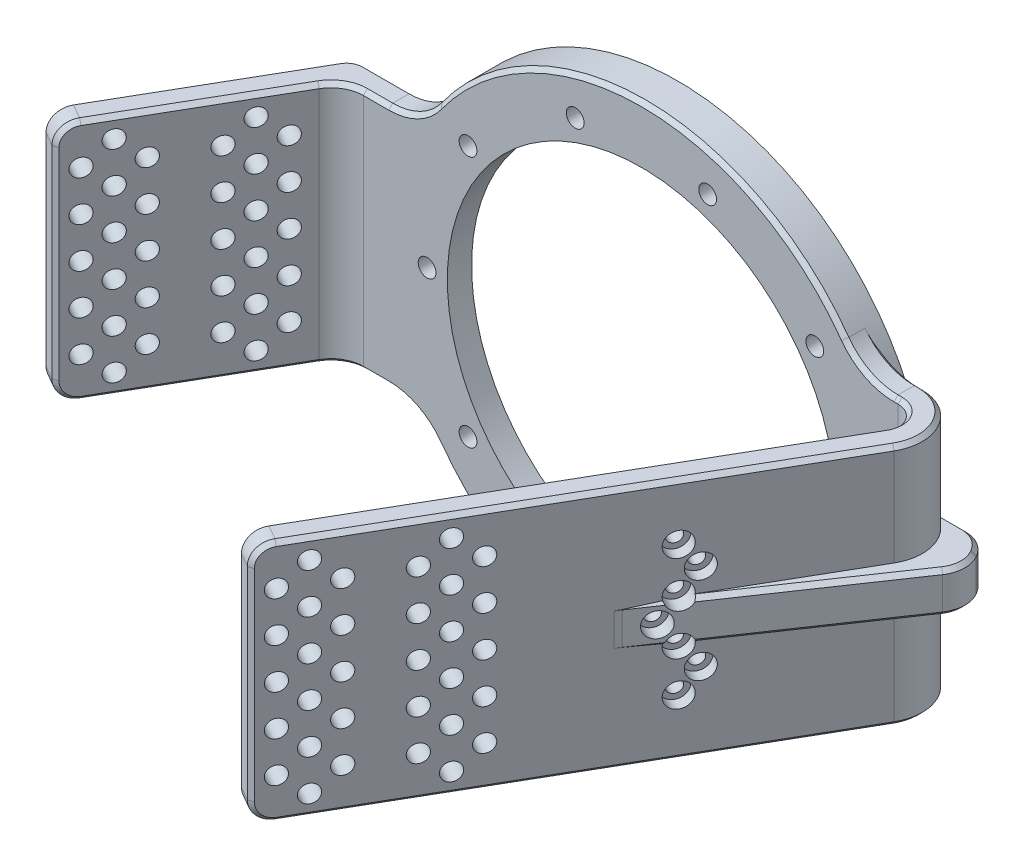
SolidWorks part; units mm, degrees
material "6061 合金"
ref_plane "前视基准面" through (0, 0, 0) normal (0, 0, 1) x (1, 0, 0)
ref_plane "上视基准面" through (0, 0, 0) normal (0, 1, 0) x (1, 0, 0)
ref_plane "右视基准面" through (0, 0, 0) normal (1, 0, 0) x (0, 0, -1)
sketch "草图1" plane through (0, 0, 0) normal (0, 0, 1) x (1, 0, 0)
  line L1 (62, 30) -> (62, -30)
  line L2 (-62, 30) -> (-62, -30)
  line L3 (62, 30) -> (54.2586, 30)
  line L4 (62, -30) -> (54.2586, -30)
  line L5 (-54.2586, 30) -> (-62, 30)
  line L7 (-54.2586, -30) -> (-62, -30)
  arc A0 (43.6921, 30) -> (43.6921, -30) centre (0, 0) ccw construction
  arc A1 (51.9615, 30) -> (-51.9615, 30) centre (0, 0) ccw construction
  circle A2 centre (0, 0) radius 48
  arc A3 (54.2586, 30) -> (-54.2586, 30) centre (0, 0) ccw
  circle A4 centre (0, 0) radius 53 construction
  circle A5 centre (0, 0) radius 60 construction
  circle A6 centre (0, 0) radius 62 construction
  arc A8 (-54.2586, -30) -> (54.2586, -30) centre (0, 0) ccw
  point P12 (62, 0)
  point P15 (-62, 0)
  dimension "D1" = 5
  dimension "D2" = 2
extrude "凸台-拉伸1" add sketch "草图1" along normal blind 6
sketch "草图2" plane through (0, -30, 0) normal (0, -1, 0) x (1, 0, 0)
  line L0 (-99.738, 51.6754) -> (-73.3673, 6)
  line L1 (-104.9342, 48.6754) -> (-76.8314, 0)
  line L2 (-62, 0) -> (-54.2586, 0) construction
  line L3 (-62, 6) -> (-54.2586, 6) construction
  line L4 (-76.8314, 0) -> (-62, 0)
  line L5 (-73.3673, 6) -> (-62, 6)
  line L6 (9.3812, 114.6754) -> (72.125, 6)
  line L7 (14.5773, 117.6754) -> (82.5173, 0)
  line L8 (-104.9342, 48.6754) -> (-81.0842, 7.366) construction
  line L9 (-99.738, 51.6754) -> (-75.888, 10.366) construction
  line L10 (9.3812, 114.6754) -> (33.2312, 73.366) construction
  line L11 (14.5773, 117.6754) -> (38.4273, 76.366) construction
  line L12 (-104.9342, 48.6754) -> (-99.738, 51.6754)
  line L13 (9.3812, 114.6754) -> (14.5773, 117.6754)
  line L14 (-62, 0) -> (-62, 6)
  line L15 (62, 6) -> (62, 0)
  line L16 (62, 6) -> (72.125, 6)
  line L17 (62, 0) -> (82.5173, 0)
  dimension "D1" = 6
  dimension "D2" = 6
extrude "凸台-拉伸2" add sketch "草图2" against normal up to surface (60 mm away) up to face at (-58.1293, 30, 3)
fillet "圆角3" radius 8 1 edges at (-73.3673, 0, 6)
fillet "圆角4" radius 5 1 edges at (-76.8314, 0, 0)
fillet "圆角6" radius 5 4 edges at (11.9793, -30, 116.1754) (11.9793, 30, 116.1754) (-102.3361, 30, 50.1754) (-102.3361, -30, 50.1754)
fillet "圆角7" radius 5 1 edges at (72.125, 0, 6)
fillet "圆角8" radius 11 1 edges at (82.5173, 0, 0)
fillet "圆角9" radius 15 4 edges at (-54.2586, -30, 3) (-54.2586, 30, 3) (54.2586, 30, 3) (54.2586, -30, 3)
sketch "草图3" plane through (61.888, 0, 35.731) normal (0.866, 0, 0.5) x (0.5, 0, -0.866)
  line L1 (-51.9212, 20) -> (-51.9212, -20) construction
  circle A0 centre (-89.6212, 0) radius 2.2
  circle A1 centre (-89.6212, 10) radius 2.2
  circle A2 centre (-89.6212, 20) radius 2.2
  circle A3 centre (-89.6212, -10) radius 2.2
  circle A4 centre (-89.6212, -20) radius 2.2
  circle A5 centre (-83.6212, 5) radius 2.2
  circle A6 centre (-83.6212, 15) radius 2.2
  circle A7 centre (-83.6212, 25) radius 2.2
  circle A8 centre (-83.6212, -5) radius 2.2
  circle A9 centre (-83.6212, -15) radius 2.2
  circle A10 centre (-83.6212, -25) radius 2.2
  circle A11 centre (-77.6212, -20) radius 2.2
  circle A12 centre (-77.6212, -10) radius 2.2
  circle A13 centre (-77.6212, 0) radius 2.2
  circle A14 centre (-77.6212, 10) radius 2.2
  circle A15 centre (-77.6212, 20) radius 2.2
  circle A16 centre (-63.9212, 0) radius 2.2
  circle A17 centre (-63.9212, 10) radius 2.2
  circle A18 centre (-63.9212, 20) radius 2.2
  circle A19 centre (-63.9212, -10) radius 2.2
  circle A20 centre (-63.9212, -20) radius 2.2
  circle A21 centre (-57.9212, -25) radius 2.2
  circle A22 centre (-57.9212, -15) radius 2.2
  circle A24 centre (-57.9212, -5) radius 2.2
  circle A25 centre (-57.9212, 5) radius 2.2
  circle A26 centre (-57.9212, 15) radius 2.2
  circle A27 centre (-57.9212, 25) radius 2.2
  circle A28 centre (-51.9212, 20) radius 2.2
  circle A29 centre (-51.9212, 10) radius 2.2
  circle A30 centre (-51.9212, 0) radius 2.2
  circle A31 centre (-51.9212, -10) radius 2.2
  circle A32 centre (-51.9212, -20) radius 2.2
extrude "切除-拉伸1" cut sketch "草图3" against normal through all both and the other way through all
sketch "草图6" plane through (0, 0, 0) normal (0, 0, -1) x (-1, 0, 0)
  circle A0 centre (0, 0) radius 60
  circle A1 centre (0, 0) radius 62
extrude "凸台-拉伸3" add sketch "草图6" along normal blind 3
chamfer "倒角3" distance 1 angle 45 1 edges at (-60, 0, -3)
sketch "草图7" plane through (0, 0, -3) normal (0, 0, -1) x (-1, 0, 0)
  circle A0 centre (0, 0) radius 53 construction
  circle A1 centre (-53, 0) radius 2.2
  circle A2 centre (-42.8779, 31.1526) radius 2.2
  circle A3 centre (-16.3779, 50.406) radius 2.2
  circle A4 centre (16.3779, 50.406) radius 2.2
  circle A5 centre (42.8779, 31.1526) radius 2.2
  circle A6 centre (53, 0) radius 2.2
  circle A7 centre (42.8779, -31.1526) radius 2.2
  circle A8 centre (16.3779, -50.406) radius 2.2
  circle A9 centre (-16.3779, -50.406) radius 2.2
  circle A10 centre (-42.8779, -31.1526) radius 2.2
  point P26 (0, 0)
  dimension "D1" = 10
extrude "切除-拉伸3" cut sketch "草图7" against normal blind 11
chamfer "倒角4" distance 1 angle 45 46 edges at (-55.6444, -31.6491, 0) (-68.2133, -30, 0) (-76.4446, -30, 0.6699) (-90.3545, -30, 23.4227) (-104.2019, -28.5355, 47.4072) (-104.9342, 0, 48.6754) (-104.2019, 28.5355, 47.4072) (-90.3545, 30, 23.4227) (-55.6444, 31.6491, 0) (-76.4446, 30, 0.6699) (-68.2133, 30, 0) (-72.7485, -30, 7.0718) (-86.4573, -30, 28.6727) (-65.6152, -30, 6) (-99.0058, -28.5355, 50.4072) (-55.6444, -31.6491, 6) (-99.738, 0, 51.6754) (0, -62, 6) (-99.0058, 28.5355, 50.4072) (55.6444, -31.6491, 6) (-86.4573, 30, 28.6727) (62.9734, -30, 6) (-72.7485, 30, 7.0718) (67.7949, -30, 8.5) (-65.6152, 30, 6) (39.838, -30, 61.9227) (-55.6444, 31.6491, 6) (10.1134, -28.5355, 113.4072) (0, 62, 6) (9.3812, 0, 114.6754) (55.6444, 31.6491, 6) (10.1134, 28.5355, 113.4072) (62.9734, 30, 6) (39.838, 30, 61.9227) (67.7949, 30, 8.5) (45.0342, -30, 64.9227) (55.6444, -31.6491, 0) (62.9734, -30, 0) (72.991, -30, 5.5) (15.3096, -28.5355, 116.4072) (14.5773, 0, 117.6754) (15.3096, 28.5355, 116.4072) (55.6444, 31.6491, 0) (45.0342, 30, 64.9227) (62.9734, 30, 0) (72.991, 30, 5.5)
sketch "草图8" plane through (0, 0, 0) normal (0, 1, 0) x (1, 0, 0)
  line L0 (63.4647, 0) -> (78.4647, 0)
  line L2 (72.991, -16.5) -> (47.991, -59.8013)
  line L4 (78.4647, 0) -> (83.1358, -8.0905)
  line L5 (72.991, -16.5) -> (17.0773, -113.3453) construction
  line L7 (47.991, -59.8013) -> (83.1358, -8.0905)
  arc A0 (72.991, -16.5) -> (63.4647, 0) centre (63.4647, -11) ccw construction
  arc A1 (72.991, -16.5) -> (63.4647, 0) centre (63.4647, -11) ccw
extrude "凸台-拉伸5" add sketch "草图8" along normal mid plane 10
fillet "圆角17" radius 20 1 edges at (47.991, 0, 59.8013)
fillet "圆角19" radius 7.5 2 edges at (83.1358, 0, 8.0905) (78.4647, 0, 0)
chamfer "倒角7" distance 1 angle 45 12 edges at (48.0024, -5, 59.8084) (64.4473, -5, 35.5881) (81.7831, -5, 8.0408) (80.7066, -5, 3.883) (77.8846, -5, 1.0048) (68.7997, -5, 0) (48.0024, 5, 59.8084) (64.4473, 5, 35.5881) (81.7831, 5, 8.0408) (80.7066, 5, 3.883) (77.8846, 5, 1.0048) (68.7997, 5, 0)
sketch "草图21" plane through (61.888, 0, 35.731) normal (0.866, 0, 0.5) x (0.5, 0, -0.866)
  line L0 (-77.6212, 0) -> (-16.79, 0) construction
  line L1 (-16.79, 0) -> (-16.79, -5.375)
  line L4 (-16.79, -5.375) -> (-16.79, -10.75)
  line L5 (-16.79, -10.75) -> (-16.79, -16.125)
  line L6 (-16.79, 0) -> (-20.79, 0)
  line L7 (-16.79, 0) -> (-16.79, 5.375)
  line L8 (-16.79, 5.375) -> (-16.79, 10.75)
  line L9 (-16.79, 10.75) -> (-16.79, 16.125)
  line L10 (-16.79, 10.75) -> (-12.79, 10.75)
  line L11 (-16.79, -10.75) -> (-12.79, -10.75)
  point P9 (-16.79, -10.75)
hole_wizard "打孔尺寸(%根据)内六角圆柱头螺钉的类型0" positions "草图22" profile "草图23" counterbore size "M3" standard "GB"
sketch "草图22" plane through (61.888, 0, 35.731) normal (0.866, 0, 0.5) x (0.5, 0, -0.866)
  point P0 (-16.79, 16.125)
  point P3 (-12.79, 10.75)
  point P6 (-16.79, 5.375)
  point P9 (-20.79, 0)
  point P12 (-16.79, -5.375)
  point P15 (-12.79, -10.75)
  point P18 (-16.79, -16.125)
sketch "草图23" plane through (53.493, 16.125, 50.2716) normal (0, 1, 0) x (0.5, 0, -0.866)
  line L0 (0, 0) -> (0, 8.5215)
  line L1 (0, 8.5215) -> (1.7, 7.5)
  line L2 (1.7, 7.5) -> (1.7, 3)
  line L3 (1.7, 3) -> (3, 3)
  line L4 (3, 3) -> (3, 0)
  line L5 (3, 0) -> (0, 0)
  line L10 (0, 8.5215) -> (-1.7, 7.5) construction
  line L11 (0, -6.35) -> (0, 107.95) construction
  dimension "孔直径" = 3.4
  dimension "孔深度" = 7.5
  dimension "柱形沉头孔直径" = 6
  dimension "柱形沉头孔深度" = 3
  dimension "导头角度" = 118
sketch "草图24" plane through (59.2899, 0, 34.231) normal (0.866, 0, 0.5) x (0.5, 0, -0.866)
  circle A0 centre (-16.79, -5.375) radius 3 construction
  circle A1 centre (-16.79, 5.375) radius 3 construction
  circle A2 centre (-16.79, -5.375) radius 3
  circle A3 centre (-16.79, 5.375) radius 3
  circle A5 centre (-20.79, 0) radius 3
  circle A6 centre (-20.79, 0) radius 3
  dimension "D1" = 0
extrude "切除-拉伸4" cut sketch "草图24" along normal blind 8
sketch "草图26" plane through (0, 0, 0) normal (0, 0, -1) x (-1, 0, 0)
  line L0 (0, 0) -> (135.7281, 0) construction
  line L1 (73.9446, -29) -> (73.9446, 13.3848) construction
  line L2 (73.9446, -29) -> (73.9446, 29) construction
  circle A0 centre (73.9446, 0) radius 3
